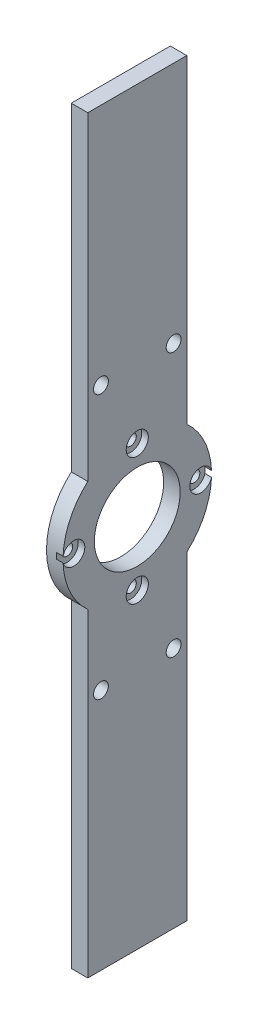
SolidWorks part; units mm, degrees
ref_plane "Спереди" through (0, 0, 0) normal (0, 0, 1) x (1, 0, 0)
ref_plane "Сверху" through (0, 0, 0) normal (0, 1, 0) x (1, 0, 0)
ref_plane "Справа" through (0, 0, 0) normal (1, 0, 0) x (0, 0, -1)
sketch "Эскиз1" plane through (0, 0, 0) normal (0, 1, 0) x (1, 0, 0)
  line L1 (0, 0) -> (5, 0)
  line L2 (0, 0) -> (0, -30)
  line L3 (0, -30) -> (5, -30)
  line L4 (5, 0) -> (5, -30)
  dimension "D1" = 5
  dimension "D2" = 30
extrude "Бобышка-Вытянуть1" add sketch "Эскиз1" along normal blind 227
sketch "Эскиз2" plane through (0, 0, 0) normal (-1, 0, 0) x (0, 0, 1)
  line L0 (30, 113.5) -> (0, 113.5) construction
  line L1 (30, 227) -> (30, 0) construction
  line L2 (0, 227) -> (0, 0) construction
  line L3 (15, 227) -> (15, 0) construction
  line L4 (0, 227) -> (30, 227) construction
  line L5 (0, 0) -> (30, 0) construction
  circle A0 centre (15, 113.5) radius 22.5
  dimension "D1" = 45
extrude "Бобышка-Вытянуть2" add sketch "Эскиз2" against normal up to surface (5 mm away) up to face at (5, 113.5, 15)
sketch "Эскиз3" plane through (0, 0, 0) normal (-1, 0, 0) x (0, 0, 1)
  circle A0 centre (15, 113.5) radius 13
  dimension "D1" = 26
extrude "Вырез-Вытянуть1" cut sketch "Эскиз3" against normal through all
sketch "Эскиз4" plane through (5, 0, 0) normal (-1, 0, 0) x (0, 0, 1)
  line L0 (15, 136) -> (15, 91) construction
  line L1 (15, 227) -> (15, 0) construction
  line L2 (37.5, 113.5) -> (-7.5, 113.5) construction
  circle A0 centre (15, 113.5) radius 19.25 construction
  circle A1 centre (15, 113.5) radius 22.5 construction
  dimension "D1" = 38.5
hole_wizard "Цековка для  винта с полукруглой головкой M31" positions "Эскиз6" profile "Эскиз5" counterbore size "M3" standard "Ansi Metric" end condition through all
sketch "Эскиз6" plane through (5, -25.0247, 7.2629) normal (-1, 0, 0) x (0, 0, 1)
  line L0 (7.7371, 161.0247) -> (7.7371, 116.0247) construction
  line L1 (30.2371, 138.5247) -> (-14.7629, 138.5247) construction
  circle A0 centre (7.7371, 138.5247) radius 19.25 construction
  point P0 (7.7371, 157.7747)
  point P6 (-11.5129, 138.5247)
  point P10 (7.7371, 119.2747)
  point P12 (26.9871, 138.5247)
sketch "Эскиз5" plane through (5, 132.75, 15) normal (0, 1, 0) x (0, 0, -1)
  line L0 (0, 0) -> (0, 5)
  line L1 (0, 5) -> (1.7, 5)
  line L3 (1.7, 5) -> (1.7, 2)
  line L4 (1.7, 2) -> (3.35, 2)
  line L5 (3.35, 2) -> (3.35, 0)
  line L7 (3.35, 0) -> (0, 0)
  line L11 (0, -6.35) -> (0, 107.95) construction
  dimension "Диаметр сквозного отверстия" = 3.4
  dimension "Глубина сквозного отверстия" = 5
  dimension "Диаметр цековки" = 6.7
  dimension "Глубина цековки" = 2
sketch "Эскиз8" plane through (5, 0, 0) normal (1, 0, 0) x (0, 0, -1)
  line L0 (-15, 227) -> (-15, 0) construction
  line L1 (-30, 227) -> (0, 227) construction
  line L2 (-30, 0) -> (0, 0) construction
  line L3 (19.447, 113.5) -> (-49.447, 113.5) construction
  line L4 (0, 227) -> (0, 130.2705) construction
  line L5 (-26, 153.5) -> (-4, 153.5) construction
  line L6 (-26, 153.5) -> (-26, 73.5) construction
  line L7 (-26, 73.5) -> (-4, 73.5) construction
  line L8 (-4, 153.5) -> (-4, 73.5) construction
  line L9 (-26, 153.5) -> (-4, 73.5) construction
  line L10 (-26, 73.5) -> (-4, 153.5) construction
  point P8 (-15, 113.5)
  point P9 (-15, 113.5)
  dimension "D1" = 4
  dimension "D2" = 80
hole_wizard "Отверстие с зазором M41" positions "Эскиз10" profile "Эскиз9" hole size "M4" standard "Ansi Metric" end condition through all
sketch "Эскиз10" plane through (5, 0, 0) normal (1, 0, 0) x (0, 0, -1)
  point P0 (-26, 153.5)
  point P3 (-4, 153.5)
  point P6 (-4, 73.5)
  point P9 (-26, 73.5)
sketch "Эскиз9" plane through (5, 153.5, 26) normal (0, 1, 0) x (0, 0, -1)
  line L0 (0, 0) -> (0, 5)
  line L1 (0, 5) -> (2.25, 5)
  line L2 (2.25, 5) -> (2.25, 0)
  line L5 (2.25, 0) -> (0, 0)
  line L11 (0, -6.35) -> (0, 107.95) construction
  dimension "Диаметр сквозного отверстия" = 4.5
  dimension "Глубина сквозного отверстия" = 5
